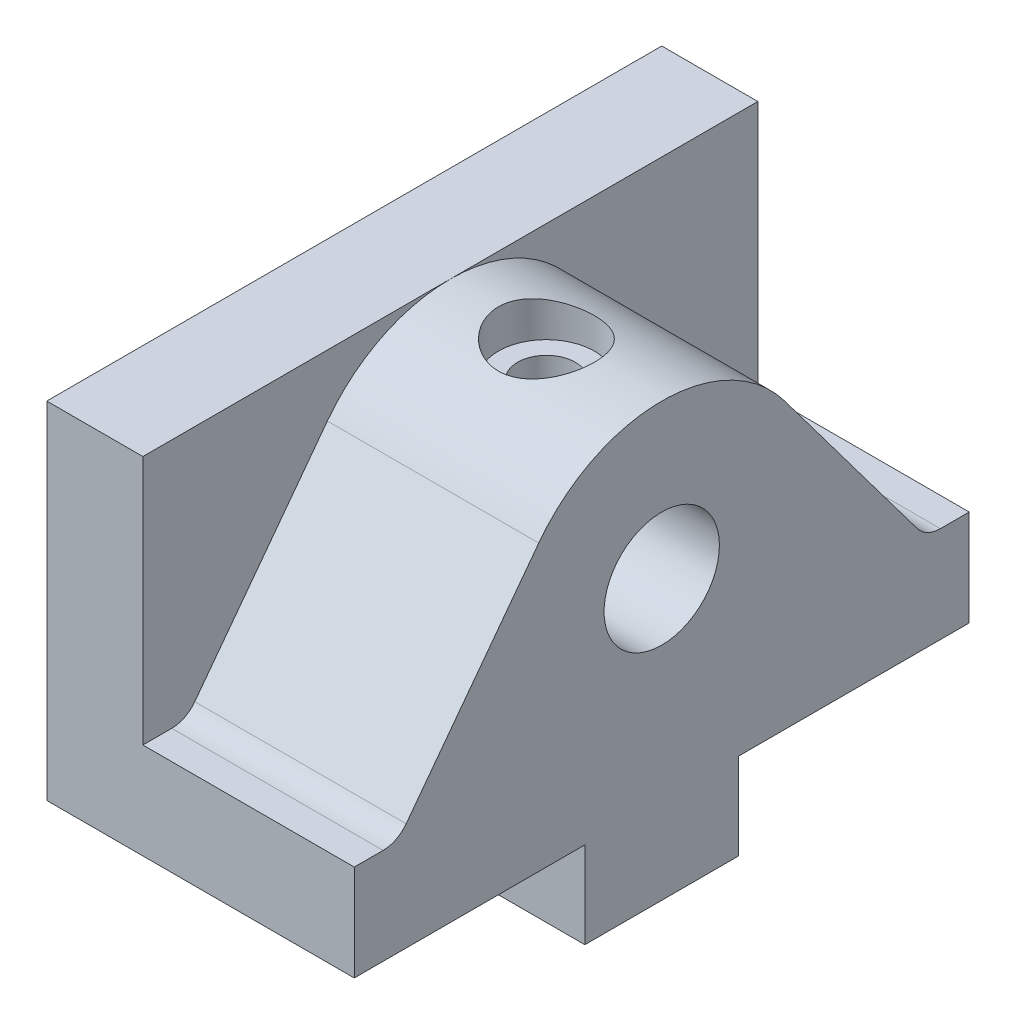
SolidWorks part; units mm, degrees
ref_plane "Front Plane" through (0, 0, 0) normal (0, 0, 1) x (1, 0, 0)
ref_plane "Top Plane" through (0, 0, 0) normal (0, 1, 0) x (1, 0, 0)
ref_plane "Right Plane" through (0, 0, 0) normal (1, 0, 0) x (0, 0, -1)
sketch "Sketch2" plane through (0, 0, 0) normal (1, 0, 0) x (0, 0, -1)
  line L0 (0, 0) -> (0, 37.8214) construction
  line L1 (-32, 45) -> (32, 45)
  line L2 (32, 45) -> (32, 9)
  line L3 (32, 9) -> (8, 9)
  line L4 (8, 9) -> (8, 0)
  line L5 (8, 0) -> (-8, 0)
  line L6 (-8, 0) -> (-8, 9)
  line L7 (-8, 9) -> (-32, 9)
  line L8 (-32, 9) -> (-32, 45)
  dimension "D1" = 16
  dimension "D2" = 64
  dimension "D3" = 9
  dimension "D4" = 36
extrude "Boss-Extrude1" add sketch "Sketch2" along normal blind 10
sketch "Sketch3" plane through (10, 0, 0) normal (1, 0, 0) x (0, 0, -1)
  line L0 (32, 9) -> (32, 45) construction
  line L1 (8, 9) -> (32, 9) construction
  line L2 (8, 0) -> (8, 9) construction
  line L3 (-8, 0) -> (8, 0) construction
  line L4 (-8, 9) -> (-8, 0) construction
  line L5 (-32, 9) -> (-8, 9) construction
  line L6 (-32, 45) -> (-32, 9) construction
  line L7 (32, 9) -> (32, 19)
  line L8 (8, 9) -> (32, 9)
  line L9 (8, 0) -> (8, 9)
  line L10 (-8, 0) -> (8, 0)
  line L11 (-8, 9) -> (-8, 0)
  line L12 (-32, 9) -> (-8, 9)
  line L13 (-32, 19) -> (-32, 9)
  line L14 (-32, 19) -> (-27.5, 19)
  line L15 (-27.5, 19) -> (-12.8, 38.6)
  line L16 (12.7848, 38.6202) -> (27.5, 19)
  line L17 (27.5, 19) -> (32, 19)
  line L18 (0, 0) -> (0, 47.2806) construction
  line L19 (32, 45) -> (-32, 45) construction
  arc A0 (-12.8, 38.6) -> (12.7848, 38.6202) centre (0, 29) cw
  point P20 (8, 40.7661)
  point P21 (12.2028, 38.9657)
  dimension "D3" = 16
  dimension "D1" = 10
  dimension "D2" = 55
extrude "Boss-Extrude2" add sketch "Sketch3" along normal blind 22
sketch "Sketch4" plane through (32, 0, 0) normal (1, 0, 0) x (0, 0, -1)
  circle A0 centre (0, 29) radius 6
  arc A1 (12.7848, 38.6202) -> (0, 45) centre (0, 29) ccw construction
  dimension "D1" = 12
extrude "Cut-Extrude1" cut sketch "Sketch4" against normal blind 24
sketch "Sketch5" plane through (0, 45, 0) normal (0, 1, 0) x (1, 0, 0)
  point P0 (20, 0)
  point P1 (0, 0)
  dimension "D1" = 20
hole_wizard "CBORE for M5 Hex Head Bolt1" positions "3DSketch1" profile "Sketch6" counterbore size "M5" standard "ANSI Metric" end condition up to next
sketch3d "3DSketch1"
  point P0 (20, 45, 0)
sketch "Sketch6" plane through (20, 45, 0) normal (1, 0, 0) x (0, 0, 1)
  line L0 (0, 0) -> (0, 10)
  line L1 (0, 10) -> (3, 10)
  line L3 (3, 10) -> (3, 4)
  line L4 (3, 4) -> (5, 4)
  line L5 (5, 4) -> (5, 0)
  line L7 (5, 0) -> (0, 0)
  line L11 (0, -6.35) -> (0, 107.95) construction
  dimension "Thru Hole Dia." = 6
  dimension "Thru Hole Depth" = 10
  dimension "C'Bore Dia." = 10
  dimension "C'Bore Depth" = 4
hole_wizard "Ø1.0mm Dowel Hole3" positions "3DSketch4" profile "Sketch9" hole size "Ø1.0" standard "ANSI Metric"
sketch3d "3DSketch4"
  line L0 (32, 0, 8) -> (32, 0, -8) construction
  point P0 (24, 0, 0)
  point P6 (0, 0, 0)
  dimension "D1" = 8
sketch "Sketch9" plane through (24, 0, 0) normal (1, 0, 0) x (0, 0, -1)
  line L0 (0, 0) -> (0, 17.7321)
  line L1 (0, 17.7321) -> (3, 16)
  line L2 (3, 16) -> (3, 0)
  line L5 (3, 0) -> (0, 0)
  line L10 (0, 17.7321) -> (-3, 16) construction
  line L11 (0, -6.35) -> (0, 107.95) construction
  dimension "Hole Dia." = 6
  dimension "Hole Depth" = 16
  dimension "Drill Angle" = 120
pattern_linear "LPattern1" count 2 spacing 16 along (-1, 0, 0) of "Ø1.0mm Dowel Hole3"
fillet "Fillet1" radius 3 2 edges at (21, 19, -27.5) (21, 19, 27.5)
